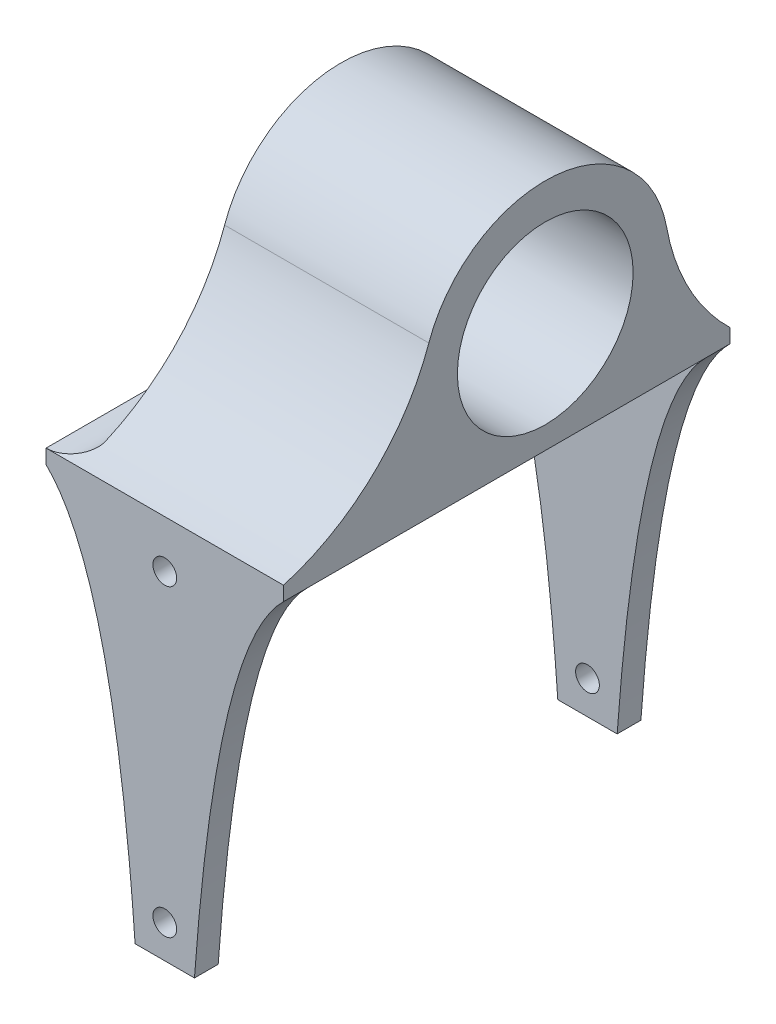
SolidWorks part; units mm, degrees
material "PLA Density Only"
ref_plane "Front Plane" through (0, 0, 0) normal (0, 0, 1) x (1, 0, 0)
ref_plane "Top Plane" through (0, 0, 0) normal (0, 1, 0) x (1, 0, 0)
ref_plane "Right Plane" through (0, 0, 0) normal (1, 0, 0) x (0, 0, -1)
sketch "Sketch2" plane through (0, 0, 0) normal (0, 0, 1) x (1, 0, 0)
  line L0 (6.25, -39) -> (-6.25, -39)
  line L1 (25, 39) -> (-25, 39)
  line L2 (0, 47.3048) -> (0, -51.1365) construction
  spline S0 degree 2 poles (-25, 39) (-10.9004, 25.3283) (-6.25, -39) knots 0 0 0 1 1 1
  spline S1 degree 2 poles (25, 39) (10.9004, 25.3283) (6.25, -39) knots 0 0 0 1 1 1
  point P8 (0, -39)
  point P9 (0, 39)
  dimension "D1" = 6.25
  dimension "D2" = 78
  dimension "D3" = 39
  dimension "D4" = 50
extrude "Boss-Extrude1" add sketch "Sketch2" along normal blind 5
sketch "Sketch3" plane through (0, 0, 0) normal (0, 0, 1) x (1, 0, 0)
  line L0 (6.25, -39) -> (-6.25, -39)
  line L1 (25, 39) -> (-25, 39)
  line L2 (0, 62.183) -> (0, -36.2583) construction
  spline S0 degree 2 poles (-25, 39) (-10.9004, 25.3283) (-6.25, -39) knots 0 0 0 1 1 1
  spline S1 degree 2 poles (25, 39) (10.9004, 25.3283) (6.25, -39) knots 0 0 0 1 1 1
  point P8 (0, -39)
  point P9 (0, 39)
  dimension "D1" = 6.25
  dimension "D2" = 78
  dimension "D3" = 39
  dimension "D4" = 50
extrude "Boss-Extrude2" add sketch "Sketch3" against normal blind 5 from offset 84 separate body offset against normal yes
sketch "Sketch9" plane through (0, 0, 0) normal (1, 0, 0) x (0, 0, -1)
  line L0 (-5, 39) -> (89, 39)
  line L1 (89, 39) -> (89, 42)
  line L2 (89, 42) -> (-5, 42)
  line L3 (-5, 42) -> (-5, 39)
  dimension "D1" = 3
extrude "Boss-Extrude7" add sketch "Sketch9" against normal blind 29 and the other way blind 21 from offset 4
sketch "Sketch5" plane through (0, 0, 5) normal (0, 0, 1) x (1, 0, 0)
  line L0 (-6.25, -39) -> (6.25, -39) construction
  circle A0 centre (0, 32) radius 2.5
  circle A1 centre (0, -32) radius 2.5
  dimension "D1" = 5
  dimension "D2" = 5
  dimension "D3" = 7
  dimension "D4" = 64
extrude "Cut-Extrude1" cut sketch "Sketch5" against normal through all both and the other way through all
sketch "Sketch10" plane through (-25, 0, 0) normal (-1, 0, 0) x (0, 0, 1)
  line L0 (5, 42) -> (5, 48)
  line L1 (5, 42) -> (-1, 42)
  line L2 (-89, 42) -> (5, 42) construction
  line L3 (-42, 65.0886) -> (-42, -9.1364) construction
  line L4 (0, 39) -> (0, -39) construction
  line L5 (-89, 42) -> (-89, 48)
  line L6 (-89, 42) -> (-83, 42)
  spline S0 degree 2 poles (5, 48) (8.1006, 42.3402) (-1, 42) knots 0 0 0 1 1 1
  spline S1 degree 2 poles (-89, 48) (-92.1006, 42.3402) (-83, 42) knots 0 0 0 1 1 1
  dimension "D1" = 6
  dimension "D2" = 6
  dimension "D3" = 42
extrude "Boss-Extrude8" [suppressed] add sketch "Sketch10" against normal blind 42 separate body
sketch "Sketch13" plane through (-25, 0, 0) normal (-1, 0, 0) x (0, 0, 1)
  line L2 (-84, 39) -> (0, 39) construction
  line L3 (-89, 42) -> (5, 42) construction
  line L5 (-89, 42) -> (5, 42) construction
  line L6 (-66.4795, 42) -> (-33.7405, 42)
  circle A0 centre (-50.11, 62.2) radius 18.5
  arc A2 (-66.4795, 42) -> (-33.7405, 42) centre (-50.11, 62.2) cw
  dimension "D1" = 18.5
  dimension "D4" = 26
  dimension "D2" = 33.89
  dimension "D3" = 23.2
extrude "Boss-Extrude9" add sketch "Sketch13" against normal up to surface (50 mm away) from offset 8.5 up to face at (25, 40, -35.4167) offset against normal yes
sketch "Sketch15" plane through (-16.5, 0, 0) normal (-1, 0, 0) x (0, 0, 1)
  line L0 (-56.1722, 65.7) -> (-50.11, 62.2) construction
  line L2 (-50.11, 62.2) -> (-34.61, 62.2) construction
  line L3 (-89, 42) -> (5, 42) construction
  line L4 (-66.4795, 42) -> (-33.7405, 42)
  circle A2 centre (-34.61, 62.2) radius 1.5
  circle A3 centre (-42.36, 48.7766) radius 1.5
  circle A4 centre (-57.86, 48.7766) radius 1.5
  circle A5 centre (-65.61, 62.2) radius 1.5
  circle A6 centre (-57.86, 75.6234) radius 1.5
  circle A7 centre (-42.36, 75.6234) radius 1.5
  arc A8 (-66.4795, 42) -> (-33.7405, 42) centre (-50.11, 62.2) cw
  circle A9 centre (-56.1722, 65.7) radius 6
  dimension "D2" = 3
  dimension "D3" = 26
  dimension "D6" = 12
  dimension "D5" = 15.5
  dimension "D7" = 7
  dimension "D8" = 150
  dimension "D4" = 6
extrude "Boss-Extrude10" add sketch "Sketch15" along normal blind 1.5
fillet "Fillet2" radius 46 2 edges at (3.5, 42, -33.7405) (3.5, 42, -66.4795)
fillet "Fillet4" radius 7 1 edges at (-18, 42, -42) second distance 2 first distance on face at (-21.5, 42, -42)
